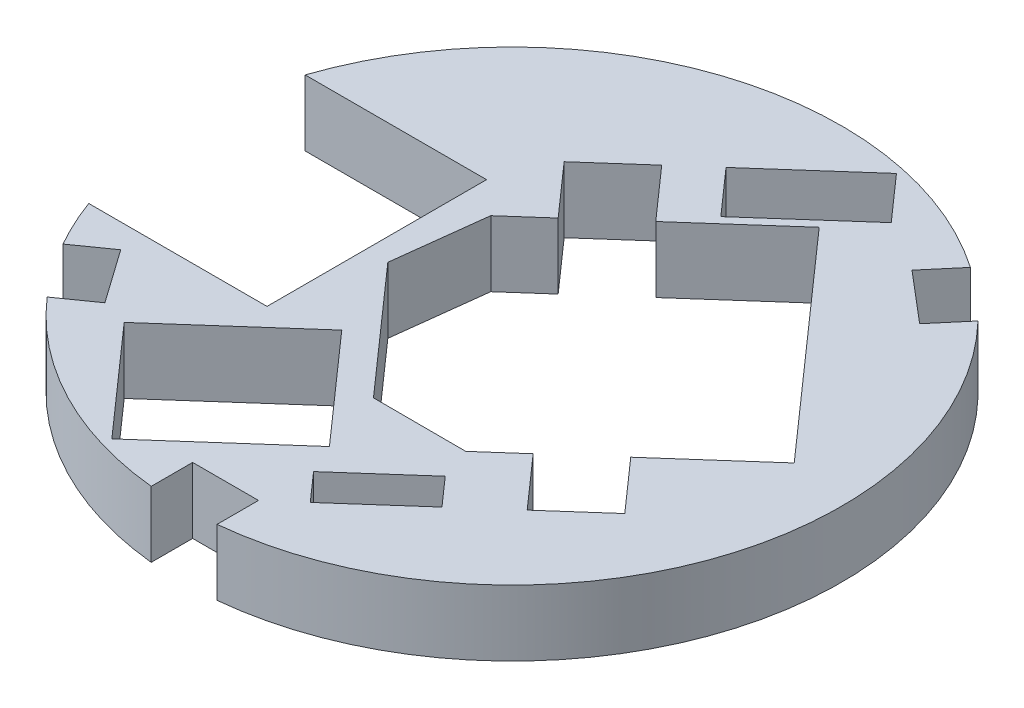
SolidWorks part; units mm, degrees
ref_plane "Front" through (0, 0, 0) normal (0, 0, 1) x (1, 0, 0)
ref_plane "Top" through (0, 0, 0) normal (0, 1, 0) x (1, 0, 0)
ref_plane "Right" through (0, 0, 0) normal (1, 0, 0) x (0, 0, -1)
sketch "Sketch1" plane through (0, 0, 0) normal (0, 1, 0) x (1, 0, 0)
  arc A0 (16.9841, 5.5245) -> (-17.1812, 4.8768) centre (0, 0) ccw
  arc A1 (-17.0607, -5.2832) -> (16.9841, -5.5245) centre (0, 0) ccw
  line B0 (-6.0563, 4.8768) -> (-17.1812, 4.8768)
  line B1 (-6.0563, 4.8768) -> (-6.0563, -5.2832)
  line B2 (-17.0607, -5.2832) -> (-6.0563, -5.2832)
  line B3 (-8.7203, -9.2308) -> (-2.4254, -3.6624)
  line B4 (-8.7203, -9.2308) -> (-4.3384, -14.1843)
  line B5 (6.0088, -5.0313) -> (-4.3384, -14.1843)
  line B6 (1.6411, -10.8279) -> (2.8023, -12.1406)
  line B7 (4.8753, -7.967) -> (1.6411, -10.8279)
  line B8 (2.8023, -12.1406) -> (6.0365, -9.2797)
  line B9 (6.0365, -9.2797) -> (4.8753, -7.967)
  line B10 (8.1292, -7.4285) -> (6.0088, -5.0313)
  line B11 (10.5264, -5.308) -> (8.1292, -7.4285)
  line B12 (8.4059, -2.9109) -> (10.5264, -5.308)
  line B13 (8.4059, -2.9109) -> (12.4201, 0.64)
  line B14 (12.4201, 0.64) -> (3.5512, 10.6661)
  line B15 (-0.463, 7.1152) -> (3.5512, 10.6661)
  line B16 (-2.5835, 9.5123) -> (-0.463, 7.1152)
  line B17 (-4.9806, 7.3918) -> (-2.5835, 9.5123)
  line B18 (-4.9806, 7.3918) -> (-2.8601, 4.9947)
  line B19 (-2.8601, 4.9947) -> (-4.5153, 3.5306)
  line B20 (-4.5153, 3.5306) -> (-5.0276, -0.7207)
  line B21 (-5.0276, -0.7207) -> (-2.4254, -3.6624)
  line B22 (-1.0044, 10.9091) -> (0.8468, 8.8164)
  line B23 (3.181, 14.6115) -> (-1.0044, 10.9091)
  line B24 (5.0322, 12.5188) -> (3.181, 14.6115)
  line B25 (0.8468, 8.8164) -> (5.0322, 12.5188)
  line B26 (16.9841, -5.5245) -> (16.9841, 5.5245)
  circle B27 centre (-10.8325, -7.6454) radius 1.143
  circle B28 centre (0, -13.2588) radius 1.143
  circle B29 centre (8.579, 10.1092) radius 1.143
sketch_block_instance "Ai_Pulsar_block_2-1"
sketch_block "Ai_Pulsar_block_2"
extrude "Boss-Extrude1" add sketch "Sketch1" along normal mid plane 3.048 contours A1 B26 A0 B0 B1 B2 B29 B28 B27 B9 B8 B6 B7 B21 B20 B19 B18 B17 B16 B15 B14 B13 B12 B11 B10 B5 B4 B3 B25 B22 B23 B24 region at (16.4898, 0, 0)
sketch "Sketch2" plane through (0, 1.524, 0) normal (0, 1, 0) x (1, 0, 0)
  line L0 (-1.524, -13.2588) -> (-1.524, -17.7948)
  line L1 (1.524, -13.2588) -> (1.524, -17.7948)
  line L2 (7.4171, 11.0953) -> (10.3521, 14.5538)
  line L3 (9.741, 9.1231) -> (12.676, 12.5816)
  line L4 (-11.7113, -6.4003) -> (-15.4173, -9.0159)
  line L5 (-9.9537, -8.8905) -> (-13.6597, -11.5061)
  line L6 (0, 0) -> (8.579, 10.1092) construction
  line L7 (0, 0) -> (0, -13.2588) construction
  line L8 (0, 0) -> (-10.8325, -7.6454) construction
  circle A0 centre (8.579, 10.1092) radius 1.524
  circle A1 centre (0, -13.2588) radius 1.524
  circle A2 centre (-10.8325, -7.6454) radius 1.524
  arc A3 (-17.0607, -5.2832) -> (16.9841, -5.5245) centre (0, 0) ccw construction
  arc A4 (16.9841, 5.5245) -> (-17.1812, 4.8768) centre (0, 0) ccw construction
  circle M1 centre (8.579, 10.1092) radius 1.143
  circle M2 centre (0, -13.2588) radius 1.143
  circle M3 centre (-10.8325, -7.6454) radius 1.143
  arc M27 (-17.0607, -5.2832) -> (16.9841, -5.5245) centre (0, 0) ccw
  arc M29 (16.9841, 5.5245) -> (-17.1812, 4.8768) centre (0, 0) ccw
  dimension "D1" = 3.048
extrude "Cut-Extrude1" cut sketch "Sketch2" against normal through all contours A2 M3 | A2 L4 L5 M27 | A1 L0 L1 M27 | A1 M2 | A0 L3 L2 M29 | A0 M1 region at (0, 1.524, 16.13) region at (-13.1783, 1.524, 9.301) region at (0, 1.524, 11.7779) region at (-12.0424, 1.524, 8.4993) region at (10.4368, 1.524, -12.2983) region at (9.0894, 1.524, -11.4994)
sketch "Sketch3" plane through (0, 1.524, 0) normal (0, 1, 0) x (1, 0, 0)
  line L0 (-12.1294, 17.1857) -> (12.1294, -17.1857) construction
  line L1 (-10.8325, -7.6454) -> (0, 0) construction
  line L2 (0, 0) -> (0, -13.2588) construction
  line L3 (0, 0) -> (8.579, 10.1092) construction
  circle A0 centre (-12.1294, 17.1857) radius 1.143
  circle A1 centre (12.1294, -17.1857) radius 1.143
  circle A2 centre (-12.1294, 17.1857) radius 3.175
  arc A3 (10.3521, 14.5538) -> (-17.1812, 4.8768) centre (0, 0) ccw construction
  arc A4 (1.524, -17.7948) -> (16.9841, -5.5245) centre (0, 0) ccw construction
  arc A5 (10.3521, 14.5538) -> (-17.1812, 4.8768) centre (0, 0) ccw
  arc A6 (1.524, -17.7948) -> (16.9841, -5.5245) centre (0, 0) ccw
  arc A7 (-13.2143, 12.015) -> (-13.6243, 14.3847) centre (-14.3419, 13.0402) ccw
  arc A8 (-8.9894, 17.656) -> (-6.8939, 16.4758) centre (-7.4822, 17.8817) ccw
  circle A9 centre (12.1294, -17.1857) radius 3.175
  arc A10 (8.9894, -17.656) -> (6.8939, -16.4758) centre (7.4822, -17.8817) ccw
  arc A11 (13.2143, -12.015) -> (13.6243, -14.3847) centre (14.3419, -13.0402) ccw
  dimension "D1" = 2.286
  dimension "D2" = 6.35
  dimension "D3" = 3.048
sketch "Sketch4" plane through (0, 1.524, 0) normal (0, 1, 0) x (1, 0, 0)
  circle A0 centre (0, 0) radius 15.2527
  circle A1 centre (0, 0) radius 20.6955
  dimension "D1" = 30.5054
extrude "Cut-Extrude2" cut sketch "Sketch4" against normal through all
sketch "Sketch5" plane through (0, 1.524, 0) normal (0, 1, 0) x (1, 0, 0)
  line L0 (-2.4254, -3.6624) -> (1.9565, -8.6159)
  line L1 (6.0088, -5.0313) -> (-4.3384, -14.1843) construction
  line L2 (1.9565, -8.6159) -> (1.0053, -9.4574)
  line L3 (1.0053, -9.4574) -> (-3.3766, -4.5038)
  line L4 (-8.7203, -9.2308) -> (-2.4254, -3.6624) construction
  line L5 (-3.3766, -4.5038) -> (-2.4254, -3.6624)
  dimension "D1" = 1.27
extrude "Boss-Extrude2" add sketch "Sketch5" against normal up to vertex (3.048 mm away) up to point (-2.4254, -1.524, 3.6624)
sketch "Sketch6" plane through (0, 1.524, 0) normal (0, 1, 0) x (1, 0, 0)
  line L0 (-11.7113, -6.4003) -> (-9.9537, -8.8905)
  line L1 (-1.524, -13.2588) -> (1.524, -13.2588)
  line L2 (1.524, -13.2588) -> (1.524, -15.1764) construction
  line L3 (7.4171, 11.0953) -> (9.741, 9.1231)
  line L4 (0.0716, -6.4852) -> (4.3536, -6.4955)
  line L5 (-5.0276, -0.7207) -> (1.9565, -8.6159) construction
  line L6 (6.0088, -5.0313) -> (1.9565, -8.6159) construction
  line L7 (-4.5153, 3.5306) -> (-5.0276, -0.7207) construction
  line L8 (-4.5153, 3.5306) -> (4.3536, -6.4955) construction
  arc A0 (1.524, -13.2588) -> (-1.524, -13.2588) centre (0, -13.2588) ccw construction
  line M1 (6.0088, -5.0313) -> (1.9565, -8.6159)
  line M2 (1.9565, -8.6159) -> (-5.0276, -0.7207)
  arc M29 (9.741, 9.1231) -> (7.4171, 11.0953) centre (8.579, 10.1092) cw
  arc M37 (-11.7113, -6.4003) -> (-9.9537, -8.8905) centre (-10.8325, -7.6454) cw
  arc M41 (-1.524, -13.2588) -> (1.524, -13.2588) centre (0, -13.2588) cw
extrude "Boss-Extrude3" add sketch "Sketch6" against normal up to vertex (3.048 mm away) contours L0 M37 | L1 M41 | L3 M29 | L4 M2 M1 region at (-10.3041, 1.524, 7.2724) region at (0, 1.524, 12.612) region at (8.1605, 1.524, -9.616) region at (2.1273, 1.524, 7.1989) up to point (-11.5204, -1.524, 9.9962)
